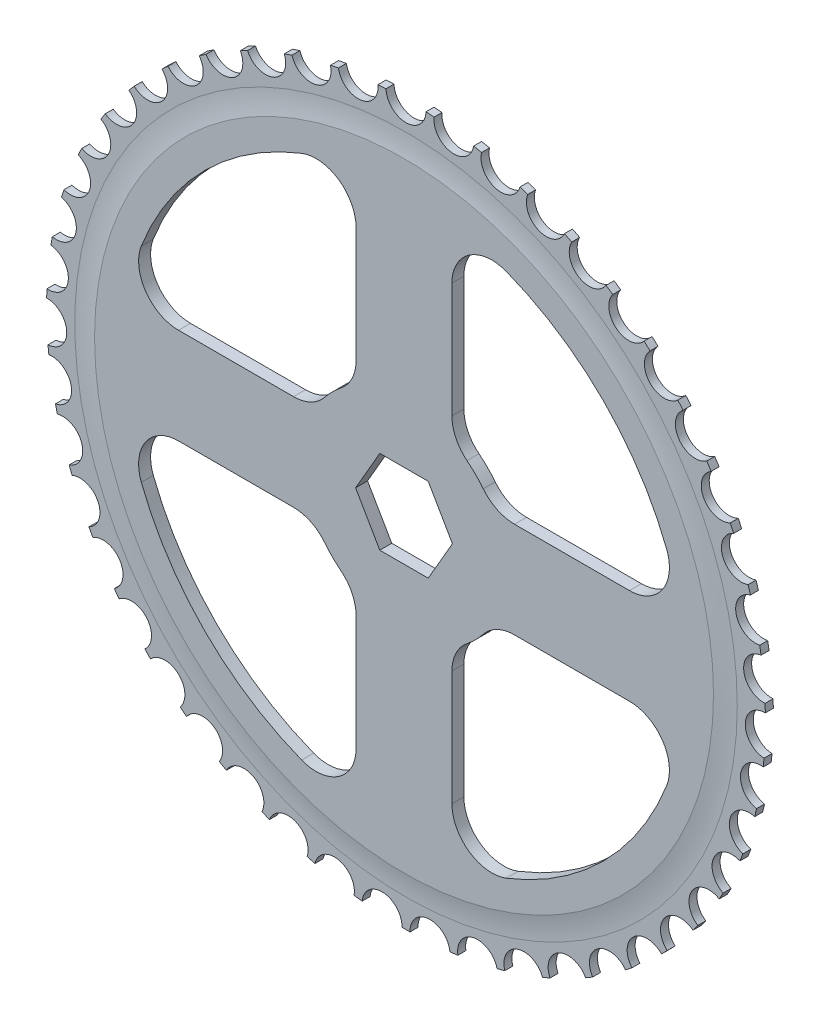
SolidWorks part; units mm, degrees
ref_plane "Front Plane" through (0, 0, 0) normal (0, 0, 1) x (1, 0, 0)
ref_plane "Top Plane" through (0, 0, 0) normal (0, 1, 0) x (1, 0, 0)
ref_plane "Right Plane" through (0, 0, 0) normal (1, 0, 0) x (0, 0, -1)
sketch "Sketch1" plane through (0, 0, 0) normal (0, 0, 1) x (1, 0, 0)
  line L1 (6.0622, 10.5) -> (-6.0622, 10.5)
  line L2 (-6.0622, 10.5) -> (-12.1244, 0)
  line L3 (-12.1244, 0) -> (-6.0622, -10.5)
  line L4 (-6.0622, -10.5) -> (6.0622, -10.5)
  line L5 (6.0622, -10.5) -> (12.1244, 0)
  line L6 (12.1244, 0) -> (6.0622, 10.5)
  circle A0 centre (0, 0) radius 10.5 construction
  arc A1 (-4.9981, 89.8611) -> (-7.0238, 89.7255) centre (0, 0) ccw
  arc A2 (-4.9981, 89.8611) -> (4.9981, 89.8611) centre (0, 90) ccw
  arc A3 (7.0238, 89.7255) -> (16.9308, 88.3931) centre (11.9958, 89.197) ccw
  arc A4 (18.9204, 87.9887) -> (28.5614, 85.3478) centre (23.7776, 86.8022) ccw
  arc A5 (30.4793, 84.6818) -> (39.6823, 80.7794) centre (35.135, 82.8585) ccw
  arc A6 (41.4944, 79.8637) -> (50.0951, 74.7695) centre (45.8655, 77.4361) ccw
  arc A7 (51.7689, 73.6205) -> (59.6139, 67.4254) centre (55.7775, 70.6319) ccw
  arc A8 (61.1197, 66.0635) -> (68.0689, 58.878) centre (64.6941, 62.5673) ccw
  arc A9 (69.3797, 57.3276) -> (75.3092, 49.28) centre (72.4563, 53.3862) ccw
  arc A10 (76.4017, 47.5687) -> (81.2057, 38.8026) centre (78.9255, 43.2524) ccw
  arc A11 (82.0603, 36.9609) -> (85.653, 27.6327) centre (83.9863, 32.3467) ccw
  arc A12 (86.2545, 25.6935) -> (88.5718, 15.9697) centre (87.5483, 20.8638) ccw
  arc A13 (88.9095, 13.9677) -> (89.9101, 4.0217) centre (89.548, 9.0086) ccw
  arc A14 (89.9779, 1.9926) -> (89.6439, -7.998) centre (89.9497, -3.0073) ccw
  arc A15 (89.4407, -10.0181) -> (87.778, -19.875) centre (88.7463, -14.9696) ccw
  arc A16 (87.3074, -21.85) -> (84.3458, -31.3973) centre (85.9592, -26.6648) ccw
  arc A17 (83.6161, -33.292) -> (79.4083, -42.3594) centre (81.6382, -37.8841) ccw
  arc A18 (78.4326, -44.1398) -> (73.0539, -52.5655) centre (75.8603, -48.4274) ccw
  arc A19 (71.8495, -54.2) -> (65.3957, -61.8336) centre (68.7287, -58.1065) ccw
  arc A20 (63.9843, -63.2931) -> (56.5706, -69.9983) centre (60.3706, -66.7487) ccw
  arc A21 (54.9773, -71.2566) -> (46.736, -76.9139) centre (50.9352, -74.1997) ccw
  arc A22 (44.9891, -77.9486) -> (36.0674, -82.4569) centre (40.5909, -80.3267) ccw
  arc A23 (34.1982, -83.2495) -> (24.7552, -86.5285) centre (29.5222, -85.0202) ccw
  arc A24 (22.797, -87.0649) -> (13.0012, -89.056) centre (17.9267, -88.1966) ccw
  arc A25 (10.989, -89.3266) -> (1.0152, -89.9943) centre (6.0113, -89.799) ccw
  arc A26 (-1.0152, -89.9943) -> (-10.989, -89.3266) centre (-6.0113, -89.799) ccw
  arc A27 (-13.0012, -89.056) -> (-22.797, -87.0649) centre (-17.9267, -88.1966) ccw
  arc A28 (-24.7552, -86.5285) -> (-34.1982, -83.2495) centre (-29.5222, -85.0202) ccw
  arc A29 (-36.0674, -82.4569) -> (-44.9891, -77.9486) centre (-40.5909, -80.3267) ccw
  arc A30 (-46.736, -76.9139) -> (-54.9773, -71.2566) centre (-50.9352, -74.1997) ccw
  arc A31 (-56.5706, -69.9983) -> (-63.9843, -63.2931) centre (-60.3706, -66.7487) ccw
  arc A32 (-65.3957, -61.8336) -> (-71.8495, -54.2) centre (-68.7287, -58.1065) ccw
  arc A33 (-73.0539, -52.5655) -> (-78.4326, -44.1398) centre (-75.8603, -48.4274) ccw
  arc A34 (-79.4083, -42.3594) -> (-83.6161, -33.292) centre (-81.6382, -37.8841) ccw
  arc A35 (-84.3458, -31.3973) -> (-87.3074, -21.85) centre (-85.9592, -26.6648) ccw
  arc A36 (-87.778, -19.875) -> (-89.4407, -10.0181) centre (-88.7463, -14.9696) ccw
  arc A37 (-89.6439, -7.998) -> (-89.9779, 1.9926) centre (-89.9497, -3.0073) ccw
  arc A38 (-89.9101, 4.0217) -> (-88.9095, 13.9677) centre (-89.548, 9.0086) ccw
  arc A39 (-88.5718, 15.9697) -> (-86.2545, 25.6935) centre (-87.5483, 20.8638) ccw
  arc A40 (-85.653, 27.6327) -> (-82.0603, 36.9609) centre (-83.9863, 32.3467) ccw
  arc A41 (-81.2057, 38.8026) -> (-76.4017, 47.5687) centre (-78.9255, 43.2524) ccw
  arc A42 (-75.3092, 49.28) -> (-69.3797, 57.3276) centre (-72.4563, 53.3862) ccw
  arc A43 (-68.0689, 58.878) -> (-61.1197, 66.0635) centre (-64.6941, 62.5673) ccw
  arc A44 (-59.6139, 67.4254) -> (-51.7689, 73.6205) centre (-55.7775, 70.6319) ccw
  arc A45 (-50.0951, 74.7695) -> (-41.4944, 79.8637) centre (-45.8655, 77.4361) ccw
  arc A46 (-39.6823, 80.7794) -> (-30.4793, 84.6818) centre (-35.135, 82.8585) ccw
  arc A47 (-28.5614, 85.3478) -> (-18.9204, 87.9887) centre (-23.7776, 86.8022) ccw
  arc A48 (-16.9308, 88.3931) -> (-7.0238, 89.7255) centre (-11.9958, 89.197) ccw
  arc A49 (7.0238, 89.7255) -> (4.9981, 89.8611) centre (0, 0) ccw
  arc A50 (18.9204, 87.9887) -> (16.9308, 88.3931) centre (0, 0) ccw
  arc A51 (30.4793, 84.6818) -> (28.5614, 85.3478) centre (0, 0) ccw
  arc A52 (41.4944, 79.8637) -> (39.6823, 80.7794) centre (0, 0) ccw
  arc A53 (51.7689, 73.6205) -> (50.0951, 74.7695) centre (0, 0) ccw
  arc A54 (61.1197, 66.0635) -> (59.6139, 67.4254) centre (0, 0) ccw
  arc A55 (69.3797, 57.3276) -> (68.0689, 58.878) centre (0, 0) ccw
  arc A56 (76.4017, 47.5687) -> (75.3092, 49.28) centre (0, 0) ccw
  arc A57 (82.0603, 36.9609) -> (81.2057, 38.8026) centre (0, 0) ccw
  arc A58 (86.2545, 25.6935) -> (85.653, 27.6327) centre (0, 0) ccw
  arc A59 (88.9095, 13.9677) -> (88.5718, 15.9697) centre (0, 0) ccw
  arc A60 (89.9779, 1.9926) -> (89.9101, 4.0217) centre (0, 0) ccw
  arc A61 (89.4407, -10.0181) -> (89.6439, -7.998) centre (0, 0) ccw
  arc A62 (87.3074, -21.85) -> (87.778, -19.875) centre (0, 0) ccw
  arc A63 (83.6161, -33.292) -> (84.3458, -31.3973) centre (0, 0) ccw
  arc A64 (78.4326, -44.1398) -> (79.4083, -42.3594) centre (0, 0) ccw
  arc A65 (71.8495, -54.2) -> (73.0539, -52.5655) centre (0, 0) ccw
  arc A66 (63.9843, -63.2931) -> (65.3957, -61.8336) centre (0, 0) ccw
  arc A67 (54.9773, -71.2566) -> (56.5706, -69.9983) centre (0, 0) ccw
  arc A68 (44.9891, -77.9486) -> (46.736, -76.9139) centre (0, 0) ccw
  arc A69 (34.1982, -83.2495) -> (36.0674, -82.4569) centre (0, 0) ccw
  arc A70 (22.797, -87.0649) -> (24.7552, -86.5285) centre (0, 0) ccw
  arc A71 (10.989, -89.3266) -> (13.0012, -89.056) centre (0, 0) ccw
  arc A72 (-1.0152, -89.9943) -> (1.0152, -89.9943) centre (0, 0) ccw
  arc A73 (-13.0012, -89.056) -> (-10.989, -89.3266) centre (0, 0) ccw
  arc A74 (-24.7552, -86.5285) -> (-22.797, -87.0649) centre (0, 0) ccw
  arc A75 (-36.0674, -82.4569) -> (-34.1982, -83.2495) centre (0, 0) ccw
  arc A76 (-46.736, -76.9139) -> (-44.9891, -77.9486) centre (0, 0) ccw
  arc A77 (-56.5706, -69.9983) -> (-54.9773, -71.2566) centre (0, 0) ccw
  arc A78 (-65.3957, -61.8336) -> (-63.9843, -63.2931) centre (0, 0) ccw
  arc A79 (-73.0539, -52.5655) -> (-71.8495, -54.2) centre (0, 0) ccw
  arc A80 (-79.4083, -42.3594) -> (-78.4326, -44.1398) centre (0, 0) ccw
  arc A81 (-84.3458, -31.3973) -> (-83.6161, -33.292) centre (0, 0) ccw
  arc A82 (-87.778, -19.875) -> (-87.3074, -21.85) centre (0, 0) ccw
  arc A83 (-89.6439, -7.998) -> (-89.4407, -10.0181) centre (0, 0) ccw
  arc A84 (-89.9101, 4.0217) -> (-89.9779, 1.9926) centre (0, 0) ccw
  arc A85 (-88.5718, 15.9697) -> (-88.9095, 13.9677) centre (0, 0) ccw
  arc A86 (-85.653, 27.6327) -> (-86.2545, 25.6935) centre (0, 0) ccw
  arc A87 (-81.2057, 38.8026) -> (-82.0603, 36.9609) centre (0, 0) ccw
  arc A88 (-75.3092, 49.28) -> (-76.4017, 47.5687) centre (0, 0) ccw
  arc A89 (-68.0689, 58.878) -> (-69.3797, 57.3276) centre (0, 0) ccw
  arc A90 (-59.6139, 67.4254) -> (-61.1197, 66.0635) centre (0, 0) ccw
  arc A91 (-50.0951, 74.7695) -> (-51.7689, 73.6205) centre (0, 0) ccw
  arc A92 (-39.6823, 80.7794) -> (-41.4944, 79.8637) centre (0, 0) ccw
  arc A93 (-28.5614, 85.3478) -> (-30.4793, 84.6818) centre (0, 0) ccw
  arc A94 (-16.9308, 88.3931) -> (-18.9204, 87.9887) centre (0, 0) ccw
  point P153 (0, 0)
  dimension "D1" = 21
  dimension "D2" = 180
  dimension "D3" = 10
  dimension "D4" = 47
extrude "Boss-Extrude1" add sketch "Sketch1" along normal mid plane 3
sketch "Sketch2" plane through (0, 0, 1.5) normal (0, 0, 1) x (1, 0, 0)
  line L0 (0, -1000) -> (0, 49000) construction
  line L1 (-1000, 0) -> (49000, 0) construction
  line L2 (12, 27.6708) -> (12, 56.4625)
  line L4 (56.4625, 12) -> (27.6708, 12)
  line L5 (56.4625, -12) -> (27.6708, -12)
  line L6 (12, -27.6708) -> (12, -56.4625)
  line L7 (-12, -27.6708) -> (-12, -56.4625)
  line L8 (-56.4625, -12) -> (-27.6708, -12)
  line L9 (-56.4625, 12) -> (-27.6708, 12)
  line L10 (-12, 27.6708) -> (-12, 56.4625)
  arc A0 (19.8433, 15.7766) -> (15.7766, 19.8433) centre (0, 0) ccw
  arc A1 (56.4625, 12) -> (65.7802, 25.6305) centre (56.4625, 22) ccw
  arc A2 (27.6708, 12) -> (19.8433, 15.7766) centre (27.6708, 22) cw
  arc A3 (12, 27.6708) -> (15.7766, 19.8433) centre (22, 27.6708) ccw
  arc A4 (65.7802, 25.6305) -> (25.6305, 65.7802) centre (0, 0) ccw
  arc A5 (12, 56.4625) -> (25.6305, 65.7802) centre (22, 56.4625) cw
  arc A6 (56.4625, -12) -> (65.7802, -25.6305) centre (56.4625, -22) cw
  arc A7 (65.7802, -25.6305) -> (25.6305, -65.7802) centre (0, 0) cw
  arc A8 (12, -56.4625) -> (25.6305, -65.7802) centre (22, -56.4625) ccw
  arc A9 (12, -27.6708) -> (15.7766, -19.8433) centre (22, -27.6708) cw
  arc A10 (19.8433, -15.7766) -> (15.7766, -19.8433) centre (0, 0) cw
  arc A11 (27.6708, -12) -> (19.8433, -15.7766) centre (27.6708, -22) ccw
  arc A12 (12, -56.4625) -> (25.6305, -65.7802) centre (22, -56.4625) ccw
  arc A13 (-12, -56.4625) -> (-25.6305, -65.7802) centre (-22, -56.4625) cw
  arc A14 (-27.6708, -12) -> (-19.8433, -15.7766) centre (-27.6708, -22) cw
  arc A15 (-19.8433, -15.7766) -> (-15.7766, -19.8433) centre (0, 0) ccw
  arc A16 (-12, -27.6708) -> (-15.7766, -19.8433) centre (-22, -27.6708) ccw
  arc A17 (-12, -56.4625) -> (-25.6305, -65.7802) centre (-22, -56.4625) cw
  arc A18 (-65.7802, -25.6305) -> (-25.6305, -65.7802) centre (0, 0) ccw
  arc A19 (-56.4625, -12) -> (-65.7802, -25.6305) centre (-56.4625, -22) ccw
  arc A20 (-56.4625, 12) -> (-65.7802, 25.6305) centre (-56.4625, 22) cw
  arc A21 (-65.7802, 25.6305) -> (-25.6305, 65.7802) centre (0, 0) cw
  arc A22 (-12, 56.4625) -> (-25.6305, 65.7802) centre (-22, 56.4625) ccw
  arc A23 (-12, 27.6708) -> (-15.7766, 19.8433) centre (-22, 27.6708) cw
  arc A24 (-19.8433, 15.7766) -> (-15.7766, 19.8433) centre (0, 0) cw
  arc A25 (-27.6708, 12) -> (-19.8433, 15.7766) centre (-27.6708, 22) ccw
  arc A26 (-12, 56.4625) -> (-25.6305, 65.7802) centre (-22, 56.4625) ccw
  point P17 (22.3307, 12)
  point P20 (12, 22.3307)
  point P22 (69.5698, 12)
  point P25 (12, 69.5698)
  dimension "D3" = 10
  dimension "D4" = 10
  dimension "D1" = 12
  dimension "D2" = 12
extrude "Cut-Extrude1" cut sketch "Sketch2" against normal through all contours L9 A25 A24 A23 L10 A22 A21 A20 | A5 L2 A3 A0 A2 L4 A1 A4 | L5 A11 A10 A9 L6 A8 A7 A6 | L8 A19 A18 A13 L7 A16 A15 A14 region at (35.6112, 35.6112, 1.5) region at (35.6112, -35.6112, 1.5) region at (-35.6112, -35.6112, 1.5) region at (-35.6112, 35.6112, 1.5)
sketch "Sketch3" plane through (0, 0, 1.5) normal (0, 0, 1) x (1, 0, 0)
  circle A0 centre (0, 0) radius 116.4595
  circle A1 centre (0, 0) radius 77.5
  dimension "D1" = 155
extrude "Cut-Extrude2" cut sketch "Sketch3" against normal blind 0.5
fillet "Fillet1" radius 30 1 edges at (77.5, 0, 1)
mirror "Mirror1" about plane through (0, 0, 0) normal (0, 0, 1) of "Fillet1", "Cut-Extrude2"
